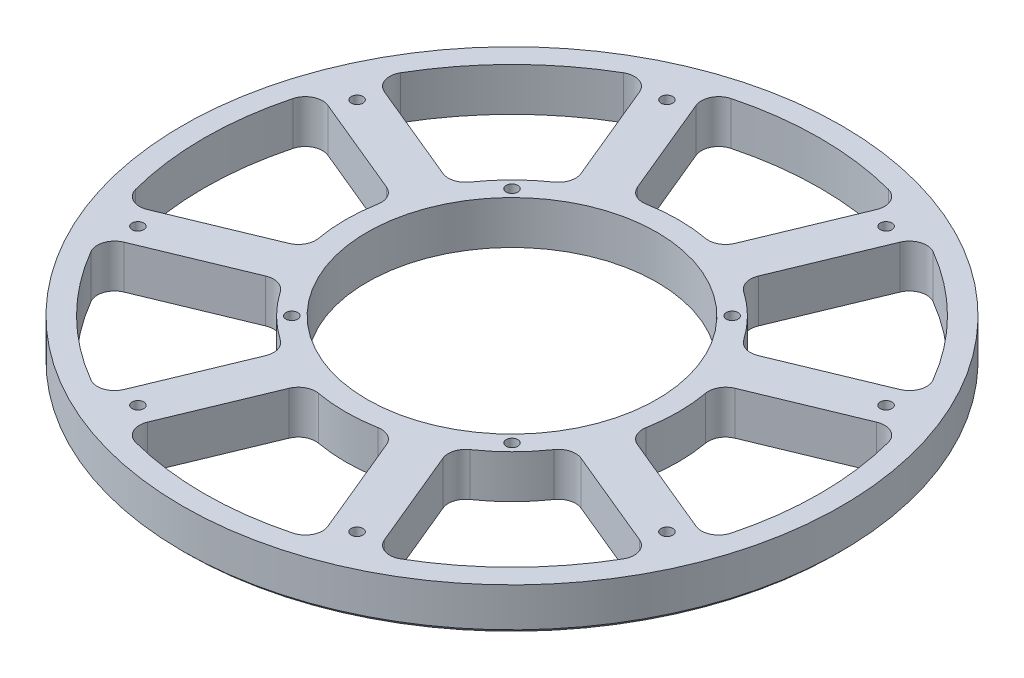
SolidWorks part; units mm, degrees
material "6061-T6 (SS)"
ref_plane "Front Plane" through (0, 0, 0) normal (0, 0, 1) x (1, 0, 0)
ref_plane "Top Plane" through (0, 0, 0) normal (0, 1, 0) x (1, 0, 0)
ref_plane "Right Plane" through (0, 0, 0) normal (1, 0, 0) x (0, 0, -1)
sketch "Sketch2" plane through (0, 0, 0) normal (1, 0, 0) x (0, 0, -1)
  line L0 (0, 0) -> (-76.2, 0)
  line L1 (-76.2, 0) -> (-76.2, 10)
  line L2 (-76.2, 10) -> (0, 10)
  line L5 (0, 10) -> (0, 0)
  dimension "D1" = 76.2
  dimension "D2" = 10
ref_axis "Axis1" through (0, -0.5, 0) along (0, 1, 0)
revolve "Revolve1" add sketch "Sketch2" angle 360 about axis through (0, -0.5, 0) along (0, 1, 0)
hole_wizard "#6-32 Tapped Hole1" positions "Sketch6" profile "Sketch7" tap size "#6-32" standard "ANSI Inch" end condition through all
sketch "Sketch6" plane through (0, 10, 0) normal (0, 1, 0) x (1, 0, 0)
  line L0 (0, 0) -> (-53.438, 129.0108) construction
  line L2 (0, 0) -> (0, 109.0908) construction
  line L3 (0, 0) -> (-70.3996, 29.1605) construction
  line L4 (0, 0) -> (-68.4315, 68.4315) construction
  circle A0 centre (0, 0) radius 76.2 construction
  point P0 (-25.3336, 61.1608)
  point P18 (-61.1608, 25.3336)
  point P27 (-25.4558, 25.4558)
  dimension "D1" = 22.5
  dimension "D2" = 66.2
  dimension "D3" = 45
  dimension "D4" = 66.2
  dimension "D6" = 22.5
  dimension "D5" = 36
sketch "Sketch7" plane through (-25.3336, 10, -61.1608) normal (1, 0, 0) x (0, 0, 1)
  line L0 (0, 0) -> (0, 10)
  line L1 (0, 10) -> (1.3525, 10)
  line L2 (1.3525, 10) -> (1.3525, 0)
  line L5 (1.3525, 0) -> (0, 0)
  line L11 (0, -6.35) -> (0, 107.95) construction
  dimension "Thread Major Dia." = 2.7051
  dimension "Thru Tap Drill Depth" = 10
pattern_circular "CirPattern3" count 4 over 360 about axis through (0, -0.5, 0) along (0, 1, 0) of "#6-32 Tapped Hole1"
sketch "Sketch8" plane through (0, 10, 0) normal (0, 1, 0) x (1, 0, 0)
  line L4 (0, 0) -> (0, 93.9995) construction
  line L5 (0, 0) -> (113.8372, 0) construction
  line L6 (-9.9891, 37.1815) -> (-22.5604, 67.5312)
  line L7 (9.9891, 37.1815) -> (22.5604, 67.5312)
  line L8 (0, 0) -> (-25.3336, 61.1608) construction
  arc A0 (-9.9891, 37.1815) -> (9.9891, 37.1815) centre (0, 0) cw
  arc A1 (-22.5604, 67.5312) -> (22.5604, 67.5312) centre (0, 0) cw
  circle A2 centre (0, 0) radius 76.2 construction
  dimension "D1" = 38.5
  dimension "D2" = 5
  dimension "D3" = 5
extrude "Cut-Extrude1" cut sketch "Sketch8" against normal through all
fillet "Fillet1" radius 4 4 edges at (9.9891, 5, -37.1815) (22.5604, 5, -67.5312) (-9.9891, 5, -37.1815) (-22.5604, 5, -67.5312)
pattern_circular "CirPattern4" count 8 over 360 about axis through (0, -0.5, 0) along (0, 1, 0) of "Cut-Extrude1", "Fillet1"
chamfer "Chamfer2" distance 1 angle 45 1 edges at (0, 0, -76.2)
sketch "Sketch9" plane through (0, 10, 0) normal (0, 1, 0) x (1, 0, 0)
  circle A0 centre (0, 0) radius 33.5
  dimension "D1" = 67
extrude "Cut-Extrude2" cut sketch "Sketch9" against normal through all
equation "\"TubeDiameter\"= 6.000in"
equation "\"D1@Sketch2\"=\"TubeDiameter\"/2"
equation "\"D2@Sketch6\"=\"TubeDiameter\"/2-10mm"
